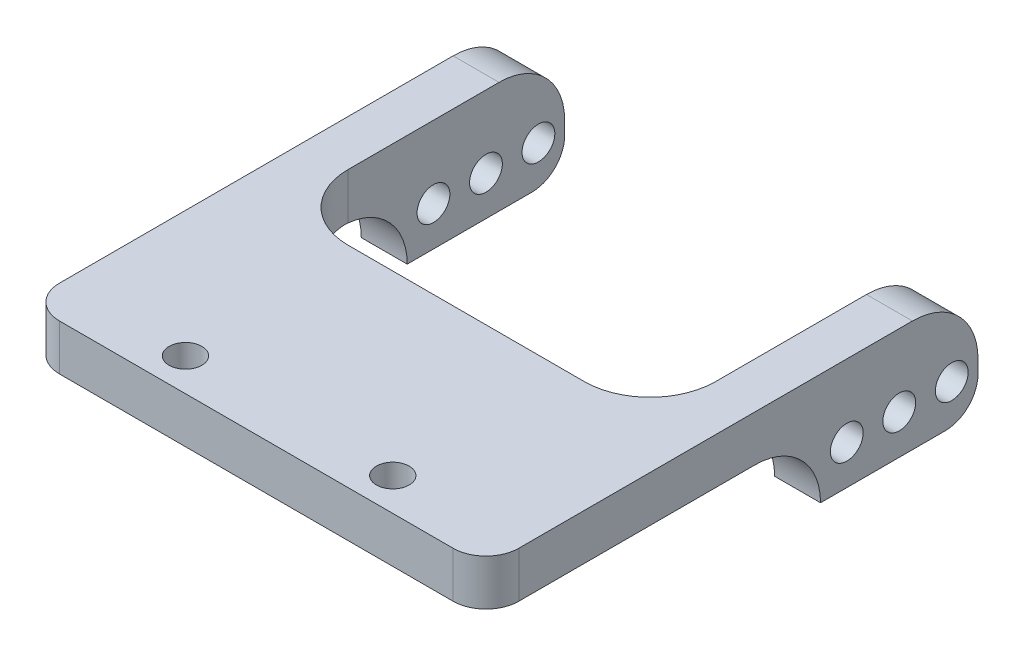
SolidWorks part; units mm, degrees
ref_plane "Front" through (0, 0, 0) normal (0, 0, 1) x (1, 0, 0)
ref_plane "Top" through (0, 0, 0) normal (0, 1, 0) x (1, 0, 0)
ref_plane "Right" through (0, 0, 0) normal (1, 0, 0) x (0, 0, -1)
sketch "草图1" plane through (0, 0, 0) normal (0, 1, 0) x (1, 0, 0)
  line L1 (0, 0) -> (7, 0)
  line L2 (0, 0) -> (0, -75)
  line L3 (0, -75) -> (70, -75)
  line L4 (70, 0) -> (70, -75)
  line L6 (63, -43) -> (63, 0)
  line L7 (35, -43) -> (63, -43)
  line L9 (7, -43) -> (7, 0)
  line L10 (7, -43) -> (35, -43)
  line L11 (63, 0) -> (70, 0)
  dimension "D1" = 75
  dimension "D2" = 70
extrude "凸台-拉伸1" add sketch "草图1" along normal blind 7
sketch "草图2" plane through (0, 0, 0) normal (0, -1, 0) x (1, 0, 0)
  line L0 (7, 43) -> (7, 0) construction
  line L1 (0, 0) -> (7, 0)
  line L2 (0, 0) -> (0, 24)
  line L3 (0, 24) -> (7, 24)
  line L4 (7, 0) -> (7, 24)
  line L5 (70, 75) -> (70, 0) construction
  line L6 (63, 0) -> (70, 0)
  line L7 (63, 0) -> (63, 24)
  line L8 (63, 24) -> (70, 24)
  line L9 (70, 0) -> (70, 24)
extrude "凸台-拉伸2" add sketch "草图2" along normal blind 10
fillet "圆角1" radius 10 1 edges at (3.5, 0, 24) type face fillet first side face at (35, 0, 41.5) second side face at (3.5, -5, 24)
fillet "圆角2" radius 10 1 edges at (66.5, 0, 24) type face fillet first side face at (35, 0, 44) second side face at (66.5, -5, 24)
sketch "草图3" plane through (70, 0, 0) normal (1, 0, 0) x (0, 0, -1)
  circle A0 centre (-12, -4) radius 2.5
extrude "切除-拉伸1" cut sketch "草图3" against normal through all
fillet "圆角3" radius 10 1 edges at (3.5, 7, 0) type face fillet first side face at (35, 7, 29.5) second side face at (3.5, -1.5, 0)
fillet "圆角4" radius 10 1 edges at (66.5, 7, 0) type face fillet first side face at (66.5, -1.5, 0) second side face at (35, 7, 32)
fillet "圆角5" radius 10 1 edges at (7, 3.5, 43) type face fillet first side face at (7, -4, 14.5) second side face at (35, 3.5, 43)
fillet "圆角6" radius 10 1 edges at (63, 3.5, 43) type face fillet first side face at (40, 3.5, 43) second side face at (63, -4, 9.5)
fillet "圆角8" radius 5 1 edges at (66.5, -10, 0) type face fillet first side face at (66.5, -6.5, 0) second side face at (66.5, -10, 12)
fillet "圆角9" radius 5 1 edges at (3.5, -10, 0) type face fillet first side face at (3.5, -6.5, 0) second side face at (3.5, -10, 12)
sketch "草图4" plane through (70, 0, 0) normal (1, 0, 0) x (0, 0, -1)
  circle A0 centre (-4, -4) radius 2.5
  circle A1 centre (-20, -4) radius 2.5
extrude "切除-拉伸2" cut sketch "草图4" against normal through all
sketch "草图5" plane through (0, 7, 0) normal (0, 1, 0) x (1, 0, 0)
  line L0 (0, -75) -> (70, -75) construction
  line L1 (35, -1075) -> (35, 48925) construction
  circle A0 centre (19.2, -70) radius 2.5
  circle A2 centre (50.8, -70) radius 2.5
  point P3 (35, -75)
  point P9 (35, 21925)
  dimension "D1" = 15.8
  dimension "D2" = 5
  dimension "D3" = 5
extrude "切除-拉伸3" cut sketch "草图5" against normal through all
fillet "圆角10" radius 5 1 edges at (0, 3.5, 75) type face fillet first side face at (0, -4, 1.5) second side face at (35, 3.5, 75)
fillet "圆角11" radius 5 1 edges at (70, 3.5, 75) type face fillet first side face at (70, -4, 1.5) second side face at (37.5, 3.5, 75)
